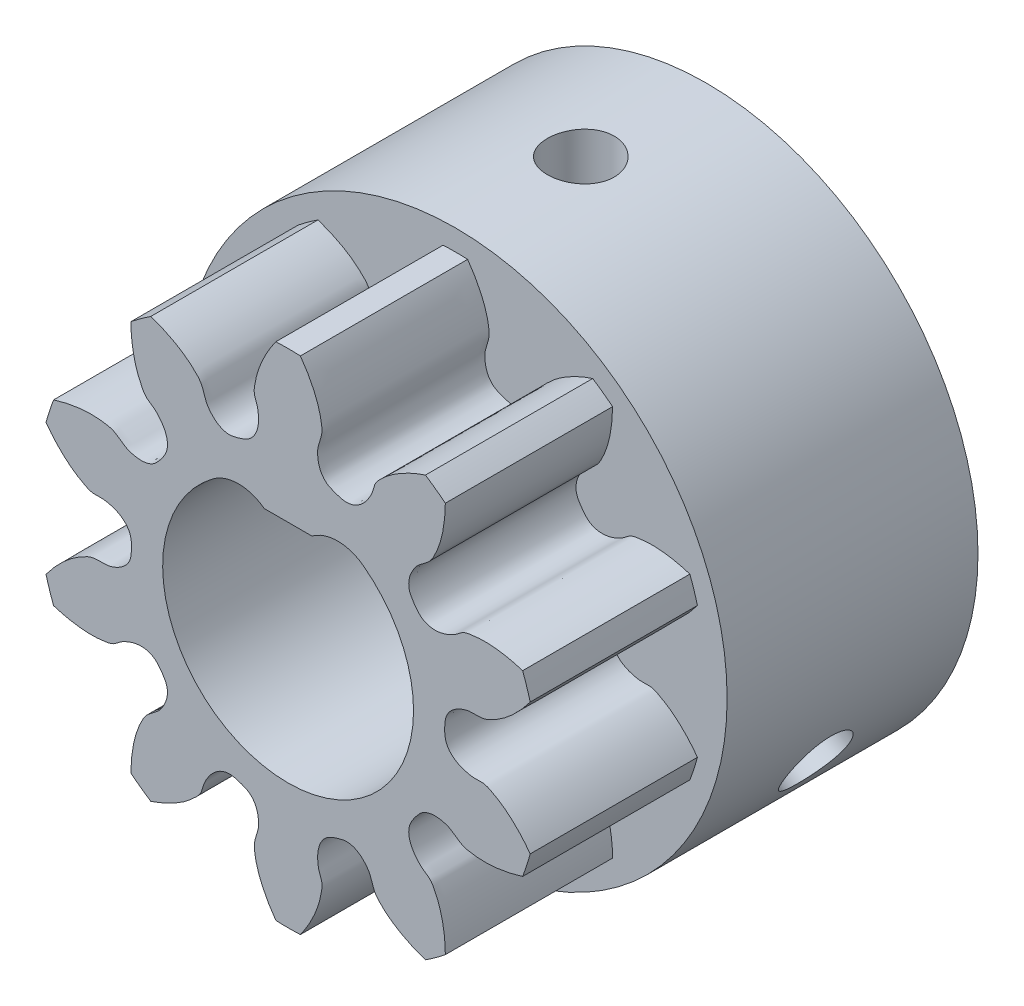
SolidWorks part; units mm, degrees
ref_plane "Front" through (0, 0, 0) normal (0, 0, 1) x (1, 0, 0)
ref_plane "Top" through (0, 0, 0) normal (0, 1, 0) x (1, 0, 0)
ref_plane "Right" through (0, 0, 0) normal (1, 0, 0) x (0, 0, -1)
ref_axis "Axis1" through (0, 0, 50) along (0, 0, -1)
sketch "SketchRevolveSun_Driver01" plane through (0, 0, 0) normal (1, 0, 0) x (0, 0, -1)
  line L0 (0, 0) -> (1, 0) construction
  line L1 (-2, 0) -> (-2, 6)
  line L2 (-2, 6) -> (2, 6)
  line L3 (2, 6) -> (2, 0)
  line L4 (2, 0) -> (-2, 0)
  dimension "Side1" = 2
  dimension "OutsideRadius" = 6
  dimension "Side2" = 2
revolve "Sun_Driver01" add sketch "SketchRevolveSun_Driver01" angle 360 about L0
sketch "SketchToothSun_Driver01" plane through (0, 0, 0) normal (0, 0, 1) x (1, 0, 0)
  arc A0 (5.8278, 1.6245) -> (5.8278, -1.6245) centre (0, 0) cw
  spline S0 degree 3 poles (5.8278, -1.6245) (5.745, -1.5079) (5.5809, -1.3019) (5.324, -1.0502) (5.094, -0.8712) (4.8857, -0.7521) (4.6797, -0.6481) (4.4634, -0.6831) (4.2696, -0.6442) (4.1044, -0.591) (3.9698, -0.5134) (3.8543, -0.4068) (3.7733, -0.2774) (3.7422, -0.1001) (3.7449, 0.078) (3.7646, 0.2534) (3.845, 0.3951) (3.9571, 0.5066) (4.1176, 0.5967) (4.3586, 0.6807) (4.6363, 0.6341) (4.8858, 0.7506) (5.094, 0.8718) (5.4375, 1.1379) (5.6757, 1.4102) (5.8278, 1.6245) knots 0 0 0 0 0.075523 0.138799 0.189829 0.228611 0.266488 0.307939 0.340187 0.370318 0.399448 0.42161 0.453029 0.478358 0.515894 0.546971 0.570783 0.600552 0.629682 0.667643 0.733512 0.771389 0.810171 0.861201 1 1 1 1
extrude "ToothExtrudeCutSun_Driver01" cut sketch "SketchToothSun_Driver01" against normal blind 2.5 and the other way blind 2.5
pattern_circular "PatternSun_Driver01" count 10 every 36 about axis through (0, 0, 50) along (0, 0, -1) of "ToothExtrudeCutSun_Driver01"
sketch "BoreRevolveSketch" plane through (0, 0, 0) normal (1, 0, 0) x (0, 0, -1)
  line L0 (0, 0) -> (1, 0) construction
  line L1 (-2.5, 0) -> (2.5, 0)
  line L2 (2.5, 0) -> (2.5, 3)
  line L3 (2.5, 3) -> (-2.5, 3)
  line L4 (-2.5, 3) -> (-2.5, 0)
  dimension "BoreSide1" = 2.5
  dimension "TaperSide1" = 3
  dimension "BoreSide2" = 2.5
  dimension "TaperSide2" = 3
revolve "BoreRevolveCut" cut sketch "BoreRevolveSketch" angle 360 about L0
sketch "AuxiliarySketchSun_Driver01" plane through (0, 0, 0) normal (0, 0, 1) x (1, 0, 0)
  circle A0 centre (0, 0) radius 5 construction
  circle A1 centre (0, 0) radius 4.6985 construction
  circle A2 centre (0, 0) radius 4.8934 construction
  circle A3 centre (0, 0) radius 6 construction
  circle A4 centre (0, 0) radius 3.75 construction
  dimension "PitchDiameter" = 10
  dimension "BaseDiameter" = 9.3969
  dimension "FormDiameter" = 9.7869
  dimension "MajorDiameter" = 12
  dimension "MinorDiameter" = 7.5
sketch "Sketch5" plane through (0, 0, -2) normal (0, 0, -1) x (-1, 0, 0)
  circle A0 centre (0, 0) radius 3
  circle A1 centre (0, 0) radius 6.5
  dimension "D1" = 13
extrude "Boss-Extrude1" add sketch "Sketch5" along normal blind 6
sketch "Sketch6" plane through (0, 0, -8) normal (0, 0, -1) x (-1, 0, 0)
  line L1 (-0.57, 2.4) -> (0.57, 2.4)
  arc A0 (1.8, 2.4) -> (-1.8, 2.4) centre (0, 0) ccw
  arc A1 (-0.57, 2.4) -> (-1.8, 2.4) centre (-1.185, 1.58) ccw
  arc A2 (1.8, 2.4) -> (0.57, 2.4) centre (1.185, 1.58) ccw
  dimension "D2" = 2.05
extrude "Boss-Extrude2" add sketch "Sketch6" against normal up to surface (10 mm away) up to face at (0, 0, 2)
ref_plane "Plane1" through (0, 2.4, 0) normal (0, -1, 0) x (1, 0, 0)
hole_wizard "Tap Drill for M2 Tap1" positions "Sketch8" profile "Sketch7" hole size "M2" standard "DIN" end condition through all
sketch "Sketch8" plane through (0, 2.4, 0) normal (0, -1, 0) x (1, 0, 0)
  line L0 (0.57, -8) -> (-0.57, -8) construction
  point P1 (0, -5)
  point P5 (0, -8)
  dimension "D1" = 3
sketch "Sketch7" plane through (0, 2.4, -5) normal (1, 0, 0) x (0, 0, -1)
  line L0 (0, 0) -> (0, 6.4792)
  line L1 (0, 6.4792) -> (0.8, 6.4792)
  line L2 (0.8, 6.4792) -> (0.8, 0)
  line L5 (0.8, 0) -> (0, 0)
  line L11 (0, -6.35) -> (0, 107.95) construction
  dimension "Thru Hole Dia." = 1.6
  dimension "Thru Hole Depth" = 6.4792
pattern_circular "CirPattern1" count 3 over 360 about axis through (0, 0, -8) along (0, 0, -1) skipping 2 of "Tap Drill for M2 Tap1"
